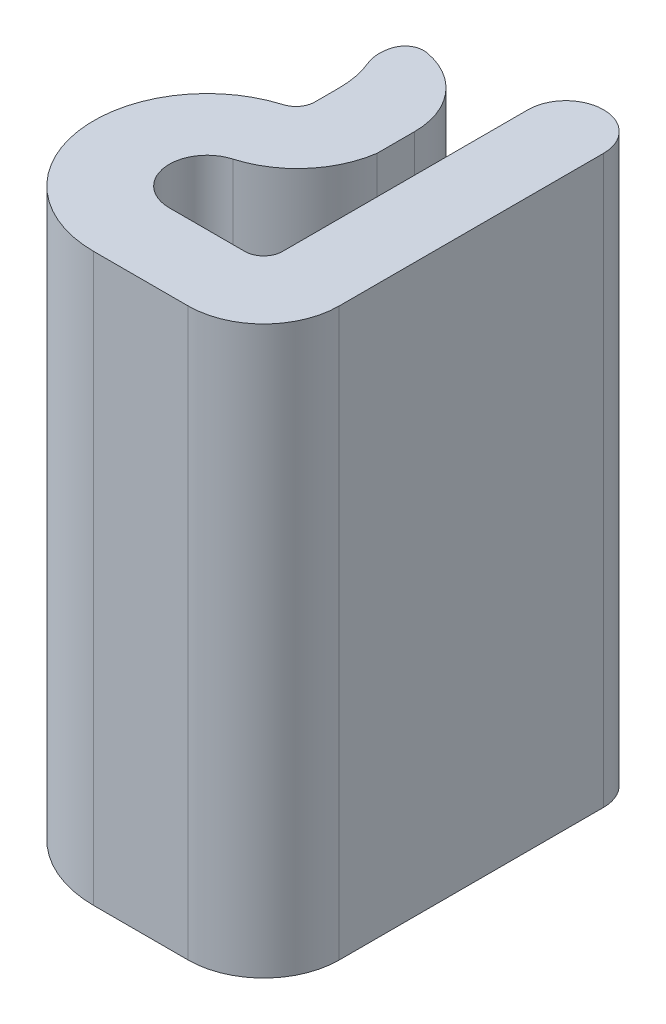
SolidWorks part; units mm, degrees
ref_plane "Front Plane" through (0, 0, 0) normal (0, 0, 1) x (1, 0, 0)
ref_plane "Top Plane" through (0, 0, 0) normal (0, 1, 0) x (1, 0, 0)
ref_plane "Right Plane" through (0, 0, 0) normal (1, 0, 0) x (0, 0, -1)
sketch "Sketch1" plane through (0, 16.5, 0) normal (0, -1, 0) x (1, 0, 0)
  line L0 (33.25, 39.5) -> (33.25, 2) construction
  line L1 (30.75, 41.5) -> (30.75, 34.5) construction
  line L2 (33.25, 39.5) -> (33.25, 2) construction
  line L3 (32.25, 34.5) -> (32.25, 35.5)
  line L4 (1.75, 39.5) -> (31.25, 39.5) construction
  line L5 (30.75, 39.5) -> (33.25, 39.5) construction
  line L6 (33.25, 39) -> (33.25, 31.5)
  line L7 (33.25, 31.5) -> (35.25, 31.5)
  line L8 (35.25, 31.5) -> (35.25, 39.5)
  line L9 (33.25, 41.5) -> (30.75, 41.5)
  line L10 (29.25, 32.5) -> (30.25, 32.5)
  line L11 (30.75, 39.5) -> (32.75, 39.5)
  line L12 (30.25, 34.5) -> (32.25, 34.5) construction
  line L13 (30.25, 34.5) -> (30.25, 35.1459)
  arc A0 (30.75, 41.5) -> (29.8929, 35.6251) centre (30.75, 38.5) ccw
  arc A1 (30.4718, 37.5395) -> (32.25, 35.5) centre (29.7763, 35.1382) cw
  arc A2 (30.25, 34.5) -> (29.25, 32.5) centre (27.75, 34.5) cw
  arc A3 (30.4718, 37.5395) -> (30.75, 39.5) centre (30.75, 38.5) cw
  arc A4 (35.25, 39.5) -> (33.25, 41.5) centre (33.25, 39.5) ccw
  arc A5 (33.25, 39) -> (32.75, 39.5) centre (32.75, 39) ccw
  arc A6 (30.25, 35.1459) -> (29.8929, 35.6251) centre (29.75, 35.1459) ccw
  arc A7 (32.25, 34.5) -> (30.25, 32.5) centre (30.25, 34.5) cw
  point P26 (30.25, 35.542)
  point P29 (32.25, 35.5)
  dimension "D6" = 1
  dimension "D7" = 1
  dimension "D8" = 3
  dimension "D4" = 2.5
  dimension "D5" = 2
  dimension "D9" = 2
  dimension "D11" = 0.5
  dimension "D3" = 1
  dimension "D13" = 0.5
  dimension "D14" = 2
  dimension "D15" = 2.5
  dimension "D16" = 2
  dimension "D1" = 2
  dimension "D2" = 2
  dimension "D10" = 8
  dimension "D12" = 2.5
  dimension "D17" = 3
extrude "Boss-Extrude1" add sketch "Sketch1" along normal blind 7.5 and the other way blind 7.5
fillet "Fillet3" radius 1 1 edges at (29.25, 16.5, 32.5)
fillet "Fillet4" radius 1 2 edges at (35.25, 16.5, 31.5) (33.25, 16.5, 31.5)
fillet "Fillet5" radius 0.5 1 edges at (30.25, 16.5, 32.5)
